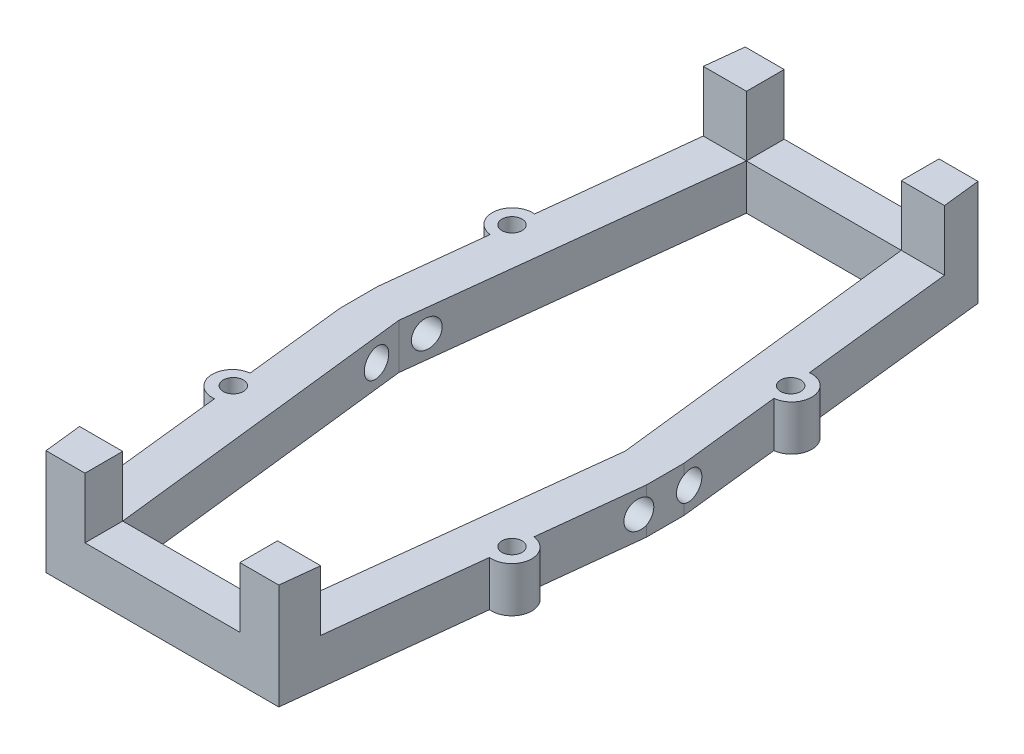
SolidWorks part; units mm, degrees
ref_plane "Front Plane" through (0, 0, 0) normal (0, 0, 1) x (1, 0, 0)
ref_plane "Top Plane" through (0, 0, 0) normal (0, 1, 0) x (1, 0, 0)
ref_plane "Right Plane" through (0, 0, 0) normal (1, 0, 0) x (0, 0, -1)
sketch "Sketch1" plane through (0, 0, 0) normal (0, 1, 0) x (1, 0, 0)
  line L0 (0, 0) -> (0, -34.75) construction
  line L1 (0, -34.75) -> (5.65, 0) construction
  line L2 (5.65, 0) -> (0, 0) construction
  line L3 (5.65, -1.875) -> (5.65, 1.875)
  line L6 (5.65, 1.875) -> (1.9, 1.875)
  line L7 (1.9, 1.875) -> (-1.875, -31)
  line L9 (-1.875, -31) -> (-17.265, -31)
  line L12 (-9.57, 6.0461) -> (-9.57, -44.986) construction
  line L21 (0, -34.75) -> (2, -34.75)
  line L22 (-19.14, -34.75) -> (0, -34.75)
  line L23 (2, -34.75) -> (4.0923, -15.9051)
  line L26 (-24.79, 0) -> (-19.14, 0) construction
  line L27 (-19.14, -34.75) -> (-24.79, 0) construction
  line L28 (-19.14, 0) -> (-19.14, -34.75) construction
  line L30 (-19.14, -34.75) -> (-21.14, -34.75)
  line L31 (-21.04, 1.875) -> (-17.265, -31)
  line L32 (-24.79, 1.875) -> (-21.04, 1.875)
  line L33 (-24.79, -1.875) -> (-24.79, 1.875)
  line L34 (4.5337, -11.9296) -> (5.65, -1.875)
  line L35 (-21.14, -34.75) -> (-23.2323, -15.9051)
  line L36 (-23.6737, -11.9296) -> (-24.79, -1.875)
  arc A0 (4.0923, -15.9051) -> (4.5337, -11.9296) centre (4.313, -13.9174) ccw
  arc A1 (-23.2323, -15.9051) -> (-23.6737, -11.9296) centre (-23.453, -13.9174) cw
  point P7 (5.65, 0)
  point P10 (0, -34.75)
  point P19 (-9.57, -34.75)
  point P20 (-9.57, -34.75)
  point P21 (-9.57, -31)
  point P22 (-9.57, -31)
  point P24 (-19.14, -34.75)
  point P25 (-24.79, 0)
  point P26 (7.9481, -13.85)
  dimension "D11" = 2
  dimension "D1" = 2
  dimension "D2" = 5.65
  dimension "D3" = 3.75
  dimension "D4" = 9.57
  dimension "D5" = 3.75
  dimension "D6" = 7.695
  dimension "D7" = 32.875
  dimension "D8" = 3.75
  dimension "D9" = 33.091
  dimension "D10" = 13.85
  dimension "D12" = 13.9174
extrude "Boss-Extrude1" add sketch "Sketch1" along normal blind 4.5
sketch "Sketch7" plane through (0, 4.5, 0) normal (0, 1, 0) x (1, 0, 0)
  line L8 (-9.57, -20.6242) -> (-9.57, -37.1202) construction
  line L21 (-1.875, -31) -> (-17.265, -31) construction
  line L26 (-1.875, -31) -> (-1.875, -34.75)
  line L27 (-21.14, -34.75) -> (2, -34.75) construction
  line L28 (-1.875, -34.75) -> (2, -34.75)
  line L29 (2, -34.75) -> (2.4163, -31)
  line L30 (2, -34.75) -> (4.0923, -15.9051) construction
  line L31 (2.4163, -31) -> (-1.875, -31)
  line L32 (-21.5563, -31) -> (-17.265, -31)
  line L33 (-21.14, -34.75) -> (-21.5563, -31)
  line L34 (-17.265, -34.75) -> (-21.14, -34.75)
  line L35 (-17.265, -31) -> (-17.265, -34.75)
  point P14 (-9.57, -31)
extrude "Boss-Extrude5" add sketch "Sketch7" along normal blind 6
sketch "Sketch8" plane through (0, 0, 0) normal (0, 1, 0) x (1, 0, 0)
  line L0 (5.65, -1.875) -> (5.65, 1.875) construction
  line L3 (-24.79, 1.875) -> (-24.79, -1.875) construction
  line L5 (-23.42, -13.85) -> (4.28, -13.85) construction
  line L6 (-23.42, -13.85) -> (-23.42, 13.85) construction
  line L7 (-23.42, 13.85) -> (4.28, 13.85) construction
  line L8 (4.28, -13.85) -> (4.28, 13.85) construction
  line L9 (-23.42, -13.85) -> (4.28, 13.85) construction
  line L10 (-23.42, 13.85) -> (4.28, -13.85) construction
  point P4 (5.65, 0)
  point P9 (-9.57, 0)
  dimension "D1" = 27.7
  dimension "D2" = 15.22
  dimension "D3" = 15.22
  dimension "D4" = 13.85
sketch "Sketch9" plane through (0, 4.5, 0) normal (0, 1, 0) x (1, 0, 0)
  circle A0 centre (4.28, 13.85) radius 1
  circle A1 centre (-23.42, 13.85) radius 1
  circle A2 centre (-23.42, -13.85) radius 1
  circle A3 centre (4.28, -13.85) radius 1
  dimension "D1" = 2
extrude "Cut-Extrude2" cut sketch "Sketch9" against normal blind 10
mirror "Mirror1" about plane through (0, 0, 0) normal (0, 0, 1) of "Boss-Extrude1", "Boss-Extrude5", "Cut-Extrude2"
sketch "Sketch11" plane through (5.65, 0, 0) normal (1, 0, 0) x (0, 0, -1)
  line L0 (0, 4.5) -> (0, 0) construction
  line L1 (13.85, 0) -> (-13.85, 0) construction
  line L2 (-1.875, 4.5) -> (1.875, 4.5) construction
  circle A0 centre (-2.5, 2.25) radius 1.375
  circle A1 centre (2.5, 2.25) radius 1.375
  point P6 (0, 2.25)
  dimension "D2" = 2.75
  dimension "D1" = 2.5
  dimension "D3" = 2.5
extrude "Cut-Extrude3" cut sketch "Sketch11" against normal through all both and the other way through all
